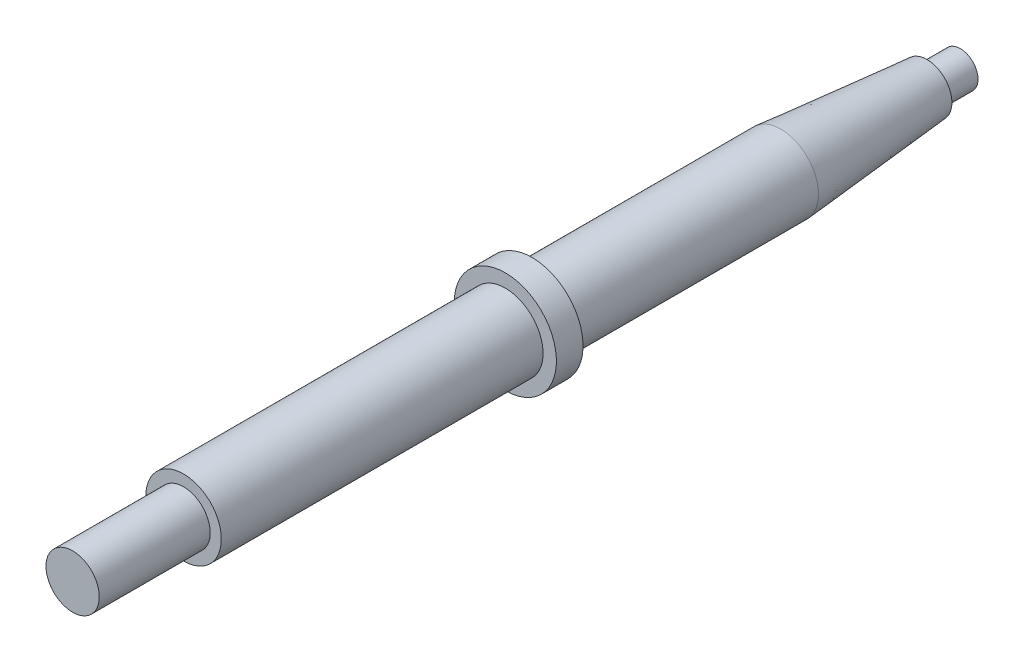
SolidWorks part; units mm, degrees
material "Plain Carbon Steel"
ref_plane "Front Plane" through (0, 0, 0) normal (0, 0, 1) x (1, 0, 0)
ref_plane "Top Plane" through (0, 0, 0) normal (0, 1, 0) x (1, 0, 0)
ref_plane "Right Plane" through (0, 0, 0) normal (1, 0, 0) x (0, 0, -1)
sketch "Base Sketch" plane through (0, 0, 0) normal (0, 1, 0) x (1, 0, 0)
  line L0 (-11.2254, 153.9926) -> (-12.8435, 153.9926)
  line L10 (-8.3435, -13.5074) -> (-8.3435, 58.9926)
  line L11 (-8.3435, 121.0526) -> (-11.2254, 153.9926)
  line L14 (-12.8435, 161.4926) -> (-16.8435, 161.4926)
  line L15 (-16.8435, 161.4926) -> (-16.8435, -13.5074)
  line L16 (-12.8435, 153.9926) -> (-12.8435, 161.4926)
  line L17 (-8.3435, -13.5074) -> (-10.8435, -13.5074)
  line L18 (-10.8435, -13.5074) -> (-10.8435, -38.5074)
  line L19 (-10.8435, -38.5074) -> (-16.8435, -38.5074)
  line L20 (-16.8435, -38.5074) -> (-16.8435, -13.5074)
  line L21 (-8.3435, 64.9926) -> (-5.3435, 64.9926)
  line L22 (-5.3435, 64.9926) -> (-5.3435, 58.9926)
  line L23 (-5.3435, 58.9926) -> (-8.3435, 58.9926)
  line L24 (-8.3435, 64.9926) -> (-8.3435, 121.0526)
  dimension "D1" = 8.5
  dimension "D2" = 185
  dimension "D3" = 32.94
  dimension "D4" = 7.5
  dimension "D6" = 4
  dimension "D5" = 6
  dimension "D7" = 25
  dimension "D8" = 200
  dimension "D10" = 6
  dimension "D11" = 56.06
  dimension "D9" = 11.5
revolve "Revolve1" add sketch "Base Sketch" angle 360 about L15
cosmetic thread "Pump Mounting Threads"
cosmetic thread "Motor Mounting Threads"
equation "\"Pump_Length\"= 33.94mm"
equation "\"Shaft_Length\"= 200mm"
equation "\"D3@Base Sketch\"=\"Pump_Length\" - 1"
equation "\"D8@Base Sketch\"=\"Shaft_Length\""
equation "\"Motor_Shaft_ID\"= 12mm"
equation "\"D5@Base Sketch\"=\"Motor_Shaft_ID\"/2"
equation "\"Motor_Shaft_Length\"= 25mm"
equation "\"D7@Base Sketch\"=\"Motor_Shaft_Length\""
equation "\"Casing_Length\"= 90mm"
equation "\"D11@Base Sketch\"=\"Casing_Length\"-\"Pump_Length\""
equation "\"Shoulder_Diameter\"= 23mm"
equation "\"D9@Base Sketch\"=\"Shoulder_Diameter\"/2"
